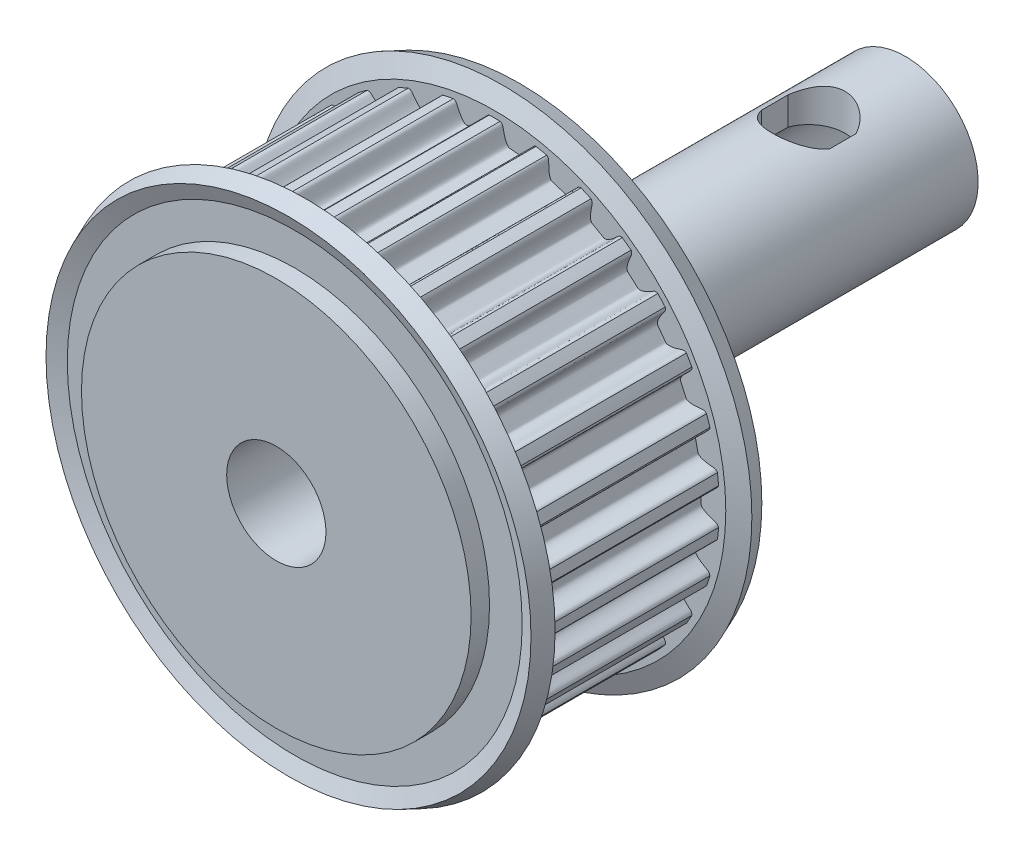
SolidWorks part; units mm, degrees
ref_plane "前视基准面" through (0, 0, 0) normal (0, 0, 1) x (1, 0, 0)
ref_plane "上视基准面" through (0, 0, 0) normal (0, 1, 0) x (1, 0, 0)
ref_plane "右视基准面" through (0, 0, 0) normal (1, 0, 0) x (0, 0, -1)
other "Configuration Table"
ref_axis "基准轴1" through (0, 0, 55) along (0, 0, -1)
sketch "SketchRevolveGearBelt01" plane through (0, 0, 0) normal (1, 0, 0) x (0, 0, -1)
  line L0 (0, 0) -> (1, 0) construction
  line L1 (5.274, 0) -> (5.274, 8.0493)
  line L2 (5.274, 8.0493) -> (4.512, 8.0493)
  line L3 (4.512, 8.0493) -> (4.512, 9.3977)
  line L4 (4.512, 9.3977) -> (4.7696, 10.0197)
  line L5 (4.7696, 10.0197) -> (4.0656, 10.3113)
  line L6 (4.0656, 10.3113) -> (3.75, 9.5493)
  line L7 (3.75, 9.5493) -> (3.75, 9.2805)
  line L8 (3.75, 9.2805) -> (-3.75, 9.2805)
  line L9 (-3.75, 9.2805) -> (-3.75, 9.5493)
  line L10 (-3.75, 9.5493) -> (-4.0656, 10.3113)
  line L11 (-4.0656, 10.3113) -> (-4.7696, 10.0197)
  line L12 (-4.7696, 10.0197) -> (-4.512, 9.3977)
  line L13 (-4.512, 9.3977) -> (-4.512, 8.0493)
  line L14 (-4.512, 8.0493) -> (-5.274, 8.0493)
  line L15 (-5.274, 8.0493) -> (-5.274, 0)
  line L16 (-5.274, 0) -> (5.274, 0)
  dimension "GearBeltFlange1OutsideLength" = 1.3484
  dimension "GearBeltFlange1X" = 0.2576
  dimension "GearBeltFlange1Y" = 0.622
  dimension "GearBeltFlangeThickness" = 0.762
  dimension "GearBeltFlangeInside" = 0.2688
  dimension "GearBeltOutsideDiameter" = 9.2805
  dimension "GearBeltFlange2X" = 0.2576
revolve "Gates_PowerGrip_GT_2mm, 6mm Belt Width" add sketch "SketchRevolveGearBelt01" angle 360 about L0
sketch "SketchToothGearBelt01" plane through (0, 0, 0) normal (0, 0, 1) x (1, 0, 0)
  arc A0 (9.2595, 0.8121) -> (9.2595, -0.8121) centre (0, 0) cw
  spline S0 degree 3 poles (9.2595, -0.8121) (9.2599, -0.7989) (9.2585, -0.7791) (9.2529, -0.7533) (9.2468, -0.7345) (9.2388, -0.7164) (9.2291, -0.6991) (9.2177, -0.6829) (9.2048, -0.6679) (9.1905, -0.6543) (9.1749, -0.6421) (9.1582, -0.6315) (9.1405, -0.6226) (9.0968, -0.6066) (9.0407, -0.5893) (8.974, -0.5675) (8.9232, -0.5498) (8.8755, -0.5322) (8.8309, -0.5145) (8.7894, -0.4969) (8.7509, -0.4793) (8.7155, -0.4616) (8.6831, -0.444) (8.6538, -0.4264) (8.6276, -0.4087) (8.6044, -0.3911) (8.5843, -0.3734) (8.5673, -0.3558) (8.5533, -0.3381) (8.5423, -0.3203) (8.5345, -0.3025) (8.5296, -0.2846) (8.5275, -0.2503) (8.5312, -0.2) (8.5317, -0.1333) (8.5327, -0.0666) (8.5328, 0) (8.5327, 0.0666) (8.5317, 0.1333) (8.5312, 0.2) (8.5275, 0.2503) (8.5296, 0.2846) (8.5345, 0.3025) (8.5423, 0.3203) (8.5533, 0.3381) (8.5673, 0.3558) (8.5843, 0.3734) (8.6044, 0.3911) (8.6276, 0.4087) (8.6538, 0.4264) (8.6831, 0.444) (8.7155, 0.4616) (8.7509, 0.4793) (8.7894, 0.4969) (8.8309, 0.5145) (8.8755, 0.5322) (8.9232, 0.5498) (8.974, 0.5675) (9.0407, 0.5893) (9.0968, 0.6066) (9.1405, 0.6226) (9.1582, 0.6315) (9.1749, 0.6421) (9.1905, 0.6543) (9.2048, 0.6679) (9.2177, 0.6829) (9.2291, 0.6991) (9.2388, 0.7164) (9.2468, 0.7345) (9.2529, 0.7533) (9.2585, 0.7791) (9.2599, 0.7989) (9.2595, 0.8121) knots 0 0 0 0 0.015924 0.023886 0.031848 0.03981 0.047771 0.055733 0.063695 0.071657 0.079619 0.087581 0.095543 0.103505 0.143783 0.166612 0.188267 0.208755 0.228086 0.24627 0.26332 0.279253 0.294087 0.307847 0.320562 0.332271 0.343022 0.352878 0.361922 0.370259 0.378023 0.385381 0.392526 0.419433 0.446289 0.473144 0.5 0.526856 0.553711 0.580567 0.607474 0.614619 0.621977 0.629741 0.638078 0.647122 0.656978 0.667729 0.679438 0.692153 0.705913 0.720747 0.73668 0.75373 0.771914 0.791245 0.811733 0.833388 0.856217 0.896495 0.904457 0.912419 0.920381 0.928343 0.936305 0.944267 0.952229 0.96019 0.968152 0.976114 0.984076 1 1 1 1
extrude "ToothExtrudeCutGearBelt01" cut sketch "SketchToothGearBelt01" against normal blind 3.75 and the other way blind 3.75
pattern_circular "Tooth Pattern, 30" count 30 every 12 about axis through (0, 0, 55) along (0, 0, -1) of "ToothExtrudeCutGearBelt01"
sketch "BoreRevolveSketch" plane through (0, 0, 0) normal (1, 0, 0) x (0, 0, -1)
  line L0 (0, 0) -> (1, 0) construction
  line L1 (-5.274, 0) -> (5.274, 0)
  line L2 (5.274, 0) -> (5.274, 5)
  line L3 (5.274, 5) -> (-5.274, 5)
  line L4 (-5.274, 5) -> (-5.274, 0)
  dimension "TaperSide1" = 5
  dimension "TaperSide2" = 5
revolve "BoreRevolveCut" cut sketch "BoreRevolveSketch" angle 360 about L0
sketch "AuxiliarySketchGearBelt01" plane through (0, 0, 0) normal (0, 0, 1) x (1, 0, 0)
  circle A0 centre (0, 0) radius 9.5493 construction
  dimension "PitchDiameter" = 19.0986
sketch "草图5" plane through (0, 0, 5.274) normal (0, 0, 1) x (1, 0, 0)
  circle A0 centre (0, 0) radius 5
extrude "凸台-拉伸1" add sketch "草图5" against normal blind 11
sketch "草图6" plane through (0, 0, -5.726) normal (0, 0, -1) x (-1, 0, 0)
  circle A0 centre (0, 0) radius 2.05
  circle A1 centre (0, 0) radius 3.15
  dimension "D1" = 4.1
  dimension "D2" = 1.1
extrude "凸台-拉伸3" add sketch "草图6" along normal blind 15
sketch "草图8" plane through (0, 0, -5.726) normal (0, 0, -1) x (-1, 0, 0)
  circle A0 centre (0, 0) radius 2.05
extrude "切除-拉伸2" cut sketch "草图8" against normal blind 15
sketch "草图9" plane through (0, 0, -20.726) normal (0, 0, -1) x (-1, 0, 0)
  line L0 (0, 0) -> (0, 1.5)
  line L1 (-1000, 1.5) -> (49000, 1.5)
  circle A0 centre (0, 0) radius 2.05
  circle M3 centre (0, 0) radius 2.05
  dimension "D1" = 1.5
extrude "凸台-拉伸4" add sketch "草图9" against normal blind 25 contours L1 M3 region at (0, 1.7227, -20.726)
sketch "草图10" plane through (0, 1.5, 0) normal (0, -1, 0) x (1, 0, 0)
  line L0 (0, -20.726) -> (0, -16.726)
  line L1 (-3.15, -20.726) -> (3.15, -20.726) construction
  line L2 (0, 55) -> (0, -55) construction
  circle A0 centre (0, -16.726) radius 1.5
  line M3 (1.3973, -20.726) -> (1.3973, 4.274)
  line M5 (-1.3973, 4.274) -> (-1.3973, -20.726)
  dimension "D2" = 3
  dimension "D1" = 4
extrude "切除-拉伸3" cut sketch "草图10" against normal blind 25 contours A0 M3 M5 region at (1.3563, 1.5, -16.726)
sketch "草图11" plane through (0, 0, -20.726) normal (0, 0, -1) x (-1, 0, 0)
  circle A0 centre (0, 0) radius 3
  circle A1 centre (0, 0) radius 3.15
  dimension "D1" = 6
extrude "切除-拉伸4" cut sketch "草图11" against normal blind 15
